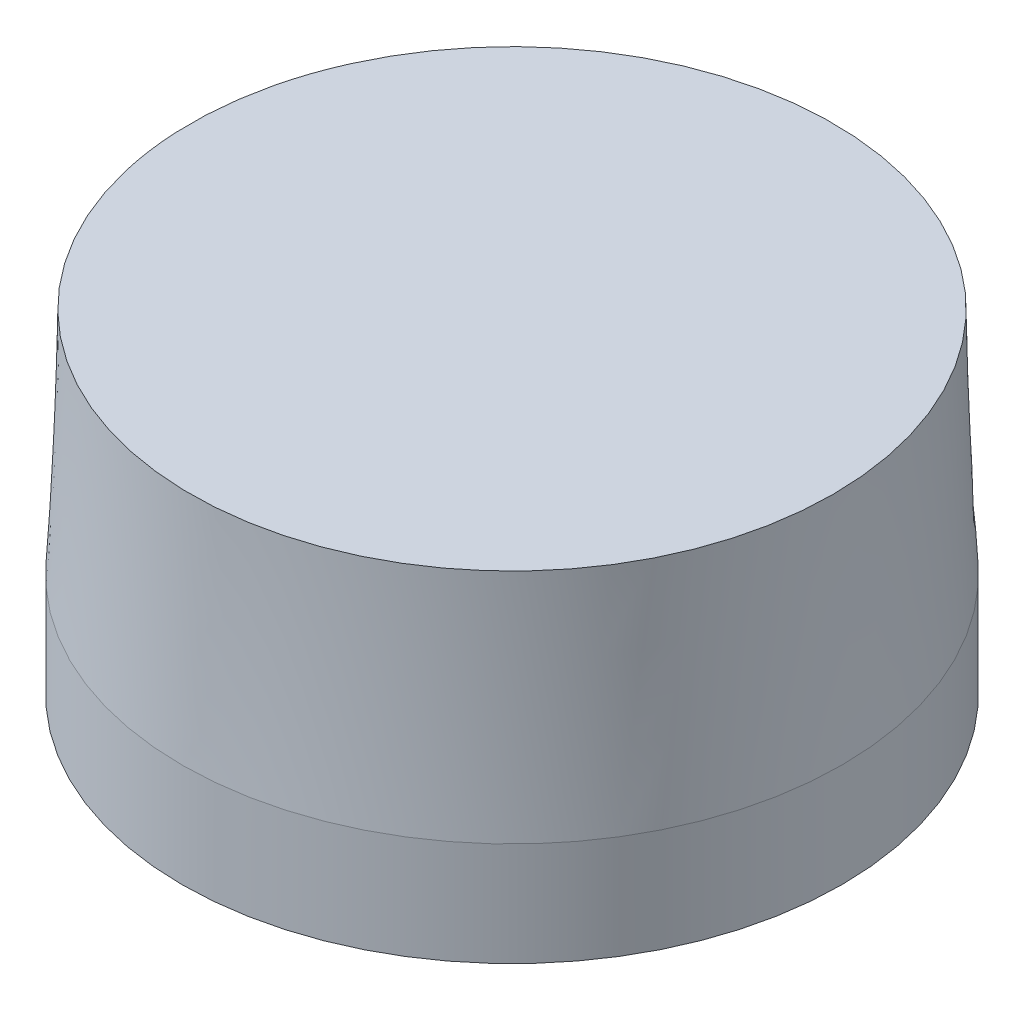
SolidWorks part; units mm, degrees
ref_plane "Front Plane" through (0, 0, 0) normal (0, 0, 1) x (1, 0, 0)
ref_plane "Top Plane" through (0, 0, 0) normal (0, 1, 0) x (1, 0, 0)
ref_plane "Right Plane" through (0, 0, 0) normal (1, 0, 0) x (0, 0, -1)
sketch "Sketch33" plane through (0, 0, 0) normal (0, 1, 0) x (1, 0, 0)
  circle A0 centre (0, 0) radius 27.9
  circle A1 centre (0, 0) radius 28.65
  circle A2 centre (0, 0) radius 26.9
extrude "Boss-Extrude6" add sketch "Sketch33" along normal blind 25 contours A0 A2 region at (-27.1109, 0, 0)
extrude "Boss-Extrude7" add sketch "Sketch33<6>" against normal blind 4 separate body contours A1 A0 region at (-28.569, 0, 0)
sketch "Sketch33<6>" plane through (0, 0, 0) normal (0, 1, 0) x (1, 0, 0) same geometry as "Sketch33"
extrude "Boss-Extrude9" add sketch "Sketch33<8>" along normal blind 5 contours A1 A0 region at (-28.569, 0, 0)
sketch "Sketch33<8>" plane through (0, 0, 0) normal (0, 1, 0) x (1, 0, 0) same geometry as "Sketch33"
extrude "Boss-Extrude10" add sketch "Sketch33<9>" along normal blind 1 from offset 22 contours A2 | A0 A2 region at (-27.1109, 0, 0) region at (0, 0, 0)
sketch "Sketch33<9>" plane through (0, 0, 0) normal (0, 1, 0) x (1, 0, 0) same geometry as "Sketch33"
loft "Loft2" add section edge at (0, 25, 27.9) section edge at (0, 5, 28.65) connector at (27.7795, 25, 2.5907) connector at (27.5719, 5, 7.7854)
sketch "Sketch36" plane through (0, 5, 0) normal (0, -1, 0) x (1, 0, 0)
  circle A0 centre (0, 0) radius 26
  circle M1 centre (0, 0) radius 26.9
extrude "Cut-Extrude1" cut sketch "Sketch36" against normal blind 19.25 contours A0 M1 | A0 region at (0, 5, 0) region at (-26.1392, 5, 0)
sketch "Sketch37" plane through (0, 24.25, 0) normal (0, -1, 0) x (1, 0, 0)
  line L0 (26.9, 0) -> (26.9, -19.7943) construction
  line L1 (19.65, 18.3708) -> (19.65, 9.1416)
  line L2 (19.65, 9.1416) -> (18.9, 9.1416)
  line L3 (18.9, 9.1416) -> (18.9, 19.1416)
  arc A1 (19.65, 18.3708) -> (18.9, 19.1416) centre (0, 0) ccw
  circle A4 centre (0, 0) radius 26.9 construction
  dimension "D3" = 7.25
  dimension "D4" = 0.75
  dimension "D5" = 10
extrude "Boss-Extrude11" add sketch "Sketch37" along normal blind 22
mirror "Mirror1" about plane through (0, 0, 0) normal (0, 0, 1) of "Boss-Extrude11"
sketch "Sketch39" plane through (18.9, 0, 0) normal (-1, 0, 0) x (0, 0, 1)
  line L0 (-9.1416, 2.25) -> (-9.1416, 24.25) construction
  line L1 (-9.1416, 15.6831) -> (-11.6416, 15.6831)
  line L2 (-9.1416, 15.6831) -> (-9.1416, 12.1831)
  line L3 (-9.1416, 12.1831) -> (-11.6416, 12.1831)
  arc A0 (-11.6416, 15.6831) -> (-11.6416, 12.1831) centre (-11.6416, 13.9331) ccw
extrude "Cut-Extrude2" cut sketch "Sketch39" against normal blind 2
